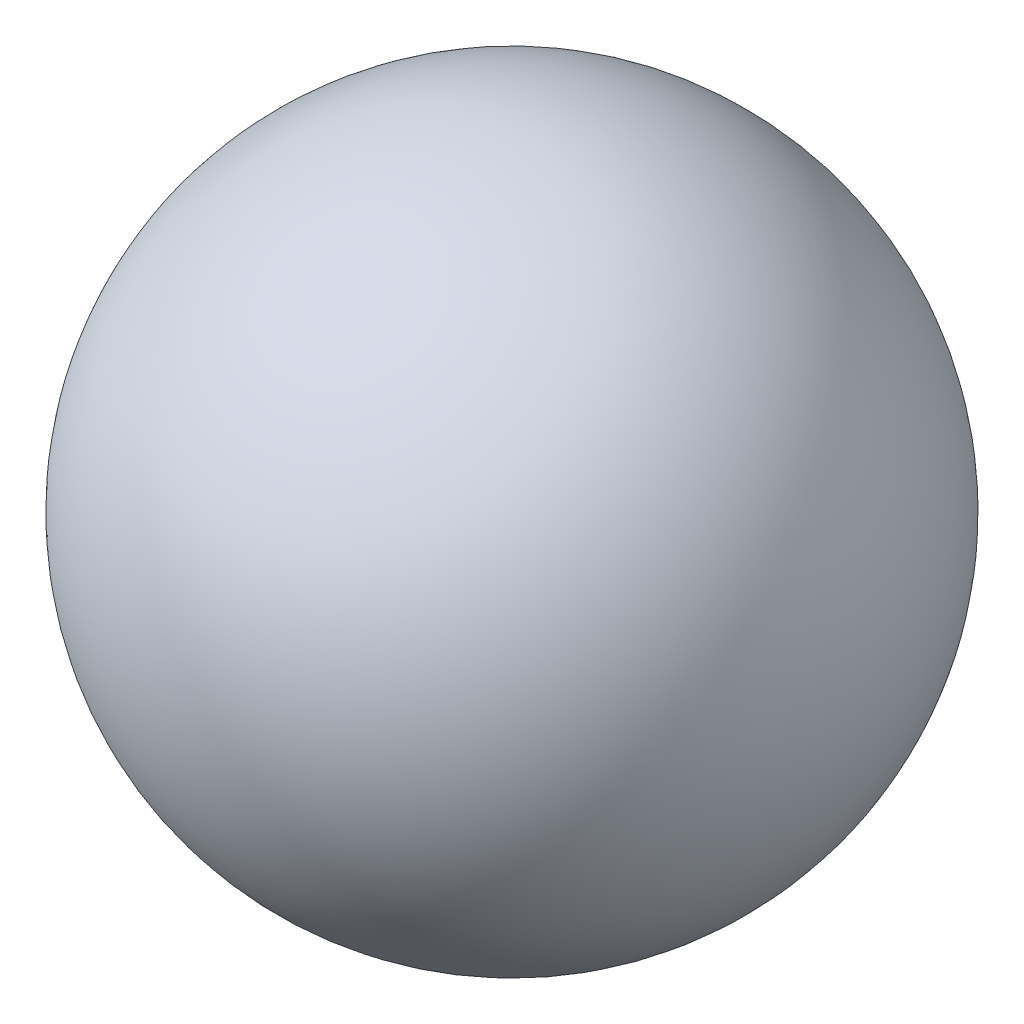
SolidWorks part; units mm, degrees
ref_plane "Front Plane" through (0, 0, 0) normal (0, 0, 1) x (1, 0, 0)
ref_plane "Top Plane" through (0, 0, 0) normal (0, 1, 0) x (1, 0, 0)
ref_plane "Right Plane" through (0, 0, 0) normal (1, 0, 0) x (0, 0, -1)
ref_plane "Plane1" through (0, 76.75, 0) normal (0, -1, 0) x (-1, 0, 0)
sketch "Sketch1" plane through (0, 76.75, 0) normal (0, -1, 0) x (-1, 0, 0)
  line L0 (38.5, 10) -> (-38.5, 10) construction
  line L1 (-13.5, -0.25) -> (7, -0.25)
  arc A0 (-13.5, -0.25) -> (7, -0.25) centre (-3.25, -0.25) ccw
  arc A1 (-13.75, 0) -> (7.25, 0) centre (-3.25, 0) ccw construction
  arc A2 (-13.75, 0) -> (7.25, 0) centre (-3.25, 0) ccw construction
  arc A3 (-13.5, -0.25) -> (7, -0.25) centre (-3.25, -0.25) cw construction
  point P7 (-3.25, -10.5)
  dimension "D1" = 20.5
revolve "Revolve1" add sketch "Sketch1" angle 360 about L1
